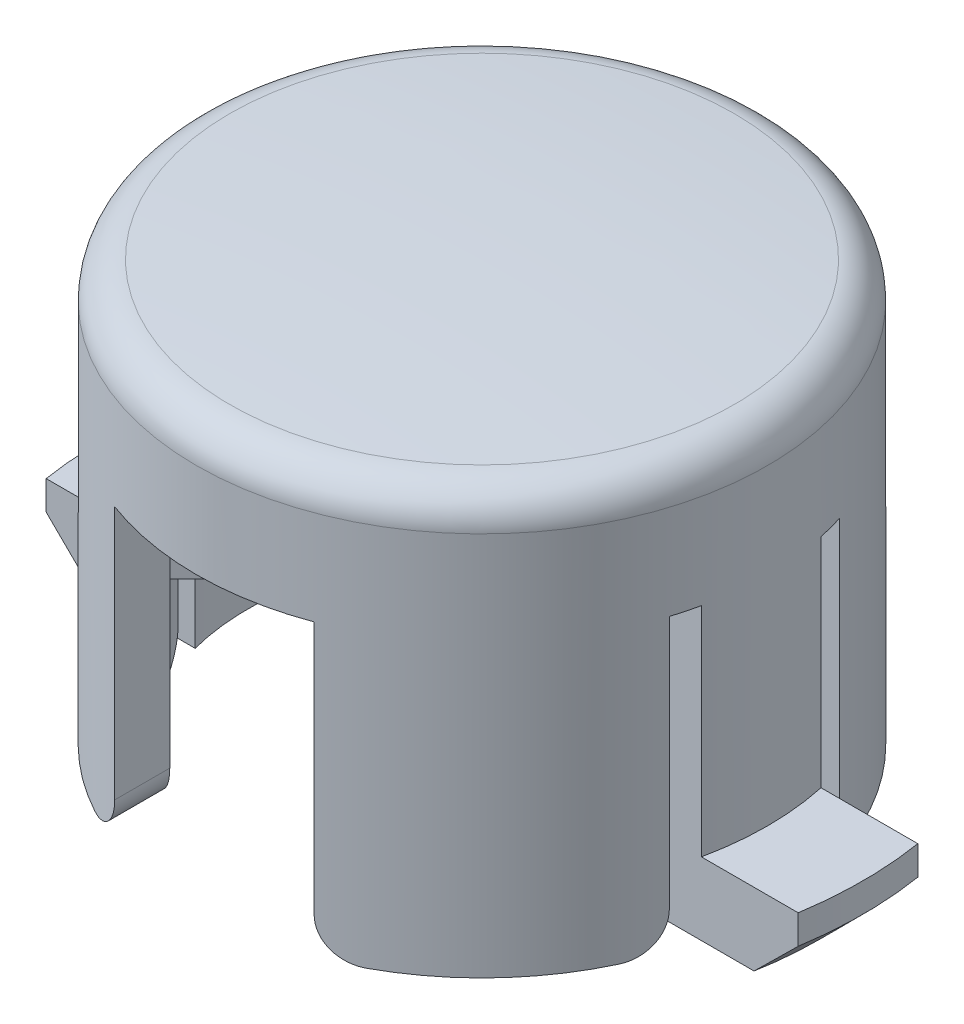
SolidWorks part; units mm, degrees
ref_plane "Front" through (0, 0, 0) normal (0, 0, 1) x (1, 0, 0)
ref_plane "Top" through (0, 0, 0) normal (0, 1, 0) x (1, 0, 0)
ref_plane "Right" through (0, 0, 0) normal (1, 0, 0) x (0, 0, -1)
sketch "Sketch1" plane through (0, 0, 0) normal (0, 0, 1) x (1, 0, 0)
  line L0 (0, 0) -> (0, 6.0399)
  line L1 (0, 6.0399) -> (21.0862, 6.0399) construction
  line L2 (0, 3.9609) -> (8.222, 3.9609)
  line L3 (10, 4.4214) -> (10, -9.0477)
  line L4 (8.222, 3.9609) -> (8.222, -9.0477)
  line L5 (8.222, -9.0477) -> (10, -9.0477)
  arc A0 (0, 6.0399) -> (8.8312, 5.6874) centre (0, -104.7583) cw
  arc A1 (10, 4.4214) -> (8.8312, 5.6874) centre (8.73, 4.4214) ccw
  dimension "D1" = 1.27
  dimension "D2" = 10
  dimension "D3" = 1.778
  dimension "D4" = 15.0876
revolve "dome/base" add sketch "Sketch1" angle 360 about L0 region at (0.181, 5.0004, 0)
sketch "Sketch2" plane through (0, -9.0477, 0) normal (0, -1, 0) x (1, 0, 0)
  line L0 (-3.4925, 0) -> (3.4925, 0) construction
  line L1 (-3.4925, 16.1782) -> (3.4925, 16.1782)
  line L2 (-3.4925, 16.1782) -> (-3.4925, -16.1782)
  line L3 (-3.4925, -16.1782) -> (3.4925, -16.1782)
  line L4 (3.4925, 16.1782) -> (3.4925, -16.1782)
  line L5 (0, 2.0955) -> (0, 0) construction
  line L6 (-20.4861, 2.9845) -> (20.4861, 2.9845)
  line L7 (-20.4861, 2.9845) -> (-20.4861, 2.0955)
  line L8 (-20.4861, 2.0955) -> (20.4861, 2.0955)
  line L9 (20.4861, 2.9845) -> (20.4861, 2.0955)
  line L10 (-20.4861, -2.9845) -> (-20.4861, -2.0955)
  line L11 (-20.4861, -2.0955) -> (20.4861, -2.0955)
  line L12 (20.4861, -2.9845) -> (20.4861, -2.0955)
  line L13 (-20.4861, -2.9845) -> (20.4861, -2.9845)
  point P6 (0, 0)
  dimension "D1" = 6.985
  dimension "D2" = 0.889
  dimension "D3" = 5.969
extrude "cutout" cut sketch "Sketch2" against normal blind 10.16 contours L6 L9 L8 L7 | L11 L12 L13 L10 | L4 L3 L2 L1
sketch "Sketch3" plane through (0, -9.0477, 0) normal (0, -1, 0) x (1, 0, 0)
  line L0 (-9.778, -2.0955) -> (-13.1693, -2.0955)
  line L1 (-9.778, 2.0955) -> (-13.1693, 2.0955)
  line L2 (-9.778, 2.0955) -> (-7.9505, 2.0955) construction
  line L3 (-9.778, -2.0955) -> (-7.9505, -2.0955) construction
  line L4 (0, -13.335) -> (0, 13.335) construction
  line L5 (9.778, 2.0955) -> (13.1693, 2.0955)
  line L6 (9.778, -2.0955) -> (13.1693, -2.0955)
  circle A0 centre (0, 0) radius 13.335
  arc A1 (-9.778, 2.0955) -> (-9.778, -2.0955) centre (0, 0) ccw construction
  arc A2 (9.778, -2.0955) -> (9.778, 2.0955) centre (0, 0) ccw construction
  arc A3 (9.778, -2.0955) -> (9.778, 2.0955) centre (0, 0) ccw
  arc A4 (-9.778, 2.0955) -> (-9.778, -2.0955) centre (0, 0) ccw
  point P13 (-10, 0)
  arc M2 (-9.778, 2.0955) -> (-9.778, -2.0955) centre (0, 0) ccw
  dimension "D1" = 26.67
extrude "tab" add sketch "Sketch3" against normal blind 2.54 contours L1 A0 L0 M2 | A3 L6 A0 L5 region at (-11.6028, -9.0477, 0) region at (11.6028, -9.0477, 0)
chamfer "tab chmf" distance 1.524 angle 45 2 edges at (13.335, -9.0477, 0) (-13.335, -9.0477, 0)
sketch "Sketch5" plane through (0, 3.9609, 0) normal (0, -1, 0) x (1, 0, 0)
  line L0 (0, 0.7184) -> (-6.1619, -5.4435)
  line L1 (-5.4435, -6.1619) -> (0, -0.7184)
  line L2 (0, 0) -> (0, -8.222) construction
  line L3 (0, -0.7184) -> (0, 0.7184) construction
  line L4 (-6.1619, 5.4435) -> (-0.7184, 0)
  line L5 (0.7184, 0) -> (-5.4435, 6.1619)
  line L6 (5.4435, 6.1619) -> (0, 0.7184)
  line L7 (0, -0.7184) -> (6.1619, 5.4435)
  line L8 (6.1619, -5.4435) -> (0.7184, 0)
  line L9 (-0.7184, 0) -> (5.4435, -6.1619)
  circle A0 centre (0, 0) radius 8.222 construction
  circle A1 centre (0, 0) radius 8.222
  point P7 (0, 0)
  circle M1 centre (0, 0) radius 8.222
  dimension "D1" = 1.016
  dimension "D3" = 45
extrude "cross" add sketch "Sketch5" along normal blind 7.62 contours L9 L0 L1 M1 | L7 L9 L8 M1 | L5 L7 L6 M1 | L0 L9 L7 L5 | L0 L5 L4 M1 region at (0, 3.9609, 0) region at (3.0847, 3.9609, 3.0847) region at (-3.0847, 3.9609, 3.0847) region at (-3.0847, 3.9609, -3.0847) region at (3.0847, 3.9609, -3.0847)
sketch "Sketch4" plane through (0, 3.9609, 0) normal (0, -1, 0) x (1, 0, 0)
  line L0 (-1.651, 0) -> (1.651, 0) construction
  line L1 (-1.651, -3.8481) -> (1.651, -3.8481)
  line L2 (-1.651, -3.8481) -> (-1.651, 3.8481)
  line L3 (-1.651, 3.8481) -> (1.651, 3.8481)
  line L4 (1.651, -3.8481) -> (1.651, 3.8481)
  point P6 (0, 0)
  dimension "D1" = 3.302
  dimension "D2" = 7.6962
extrude "box" add sketch "Sketch4" along normal offset from surface (13.0594 mm away) 0.0508 up to face at (-6.3399, -9.0477, -5.9713) offset beyond the face yes
sketch "Sketch6" plane through (0, -9.0985, 0) normal (0, -1, 0) x (1, 0, 0)
  line L8 (0.889, 3.0861) -> (-0.889, 3.0861)
  line L9 (-0.889, 3.0861) -> (-0.889, -3.0861)
  line L10 (-0.889, -3.0861) -> (0.889, -3.0861)
  line L11 (0.889, -3.0861) -> (0.889, 3.0861)
  line L12 (0.889, 3.0861) -> (-0.889, 3.0861)
  line L13 (-0.889, 3.0861) -> (-0.889, -3.0861)
  line L14 (-0.889, -3.0861) -> (0.889, -3.0861)
  line L15 (0.889, -3.0861) -> (0.889, 3.0861)
  dimension "D1" = 0.762
extrude "boxcut" cut sketch "Sketch6" against normal up to surface (13.0594 mm away) up to face at (0, 3.9609, -4.4698)
fillet "Fillet1" radius 1.27 8 edges at (3.4925, -9.0477, -8.4068) (-3.4925, -9.0477, -8.4068) (-3.4925, -9.0477, 8.4068) (3.4925, -9.0477, 8.4068) (8.6027, -9.0477, -2.9845) (8.6027, -9.0477, 2.9845) (-8.6027, -9.0477, -2.9845) (-8.6027, -9.0477, 2.9845)
